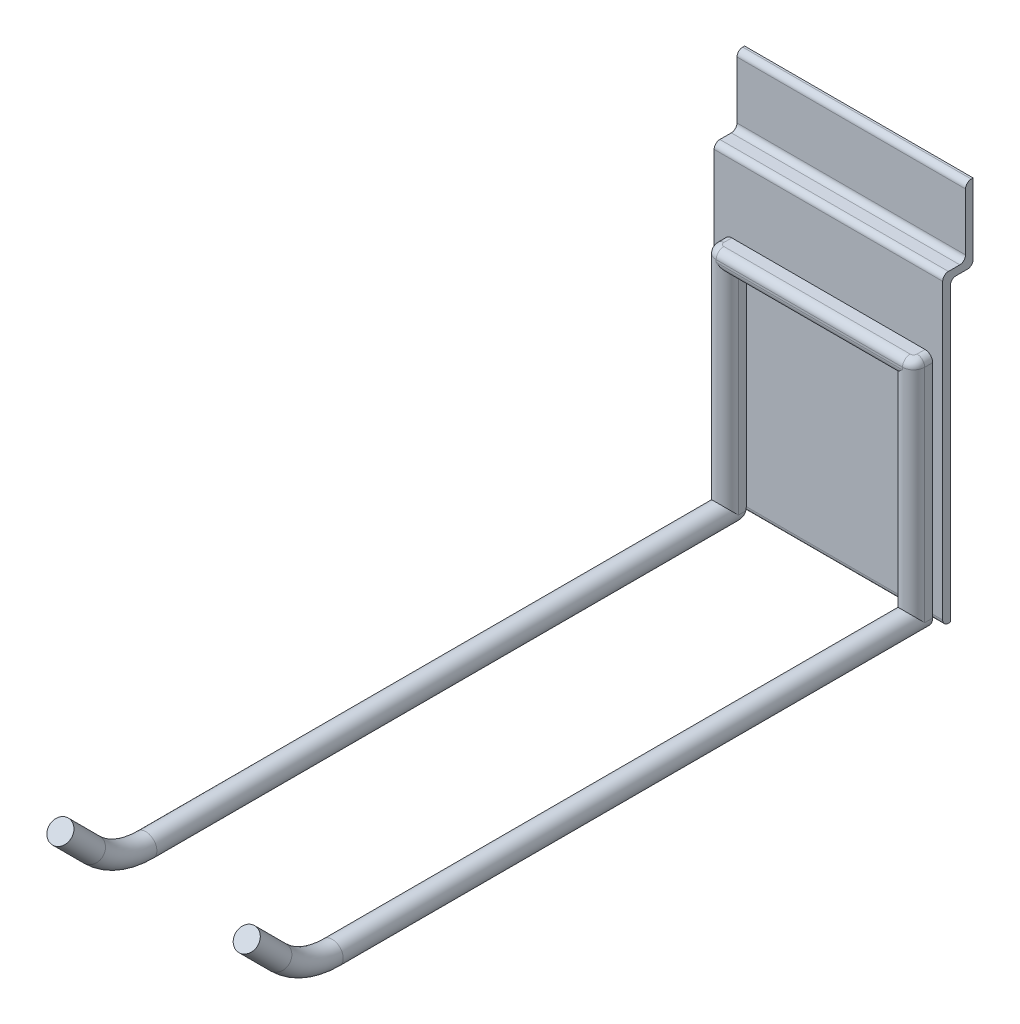
SolidWorks part; units mm, degrees
ref_plane "Front Plane" through (0, 0, 0) normal (0, 0, 1) x (1, 0, 0)
ref_plane "Top Plane" through (0, 0, 0) normal (0, 1, 0) x (1, 0, 0)
ref_plane "Right Plane" through (0, 0, 0) normal (1, 0, 0) x (0, 0, -1)
sketch "Sketch1" plane through (0, 0, 0) normal (0, 0, 1) x (1, 0, 0)
  line L1 (0, 0) -> (76.2, 0)
  line L2 (0, 0) -> (0, -101.6)
  line L3 (0, -101.6) -> (76.2, -101.6)
  line L4 (76.2, 0) -> (76.2, -101.6)
  dimension "D1" = 101.6
  dimension "D2" = 76.2
extrude "Boss-Extrude1" add sketch "Sketch1" along normal blind 2.54
sketch "Sketch3" plane through (0, 0, 0) normal (0, 0, -1) x (-1, 0, 0)
  line L0 (0, 0) -> (0, -101.6) construction
  line L1 (-76.2, 0) -> (0, 0)
  line L2 (-76.2, 0) -> (-76.2, -2.54)
  line L3 (-76.2, -2.54) -> (0, -2.54)
  line L4 (0, 0) -> (0, -2.54)
  dimension "D1" = 2.54
extrude "Boss-Extrude3" add sketch "Sketch3" along normal blind 7.62
sketch "Sketch4" plane through (0, 0, 0) normal (0, 1, 0) x (1, 0, 0)
  line L0 (76.2, -2.54) -> (76.2, 7.62) construction
  line L1 (0, 7.62) -> (76.2, 7.62)
  line L2 (0, 7.62) -> (0, 5.08)
  line L3 (0, 5.08) -> (76.2, 5.08)
  line L4 (76.2, 7.62) -> (76.2, 5.08)
  dimension "D1" = 2.54
extrude "Boss-Extrude4" add sketch "Sketch4" along normal blind 22.86
fillet "Fillet3" radius 1.905 6 edges at (38.1, -101.6, 2.54) (38.1, 0, 2.54) (38.1, 0, -5.08) (38.1, 22.86, -5.08) (38.1, -2.54, -7.62) (38.1, -2.54, 0)
sketch "Sketch5" plane through (0, 0, 2.54) normal (0, 0, 1) x (1, 0, 0)
  line L0 (3.3436, -104.5061) -> (3.3436, -24.5234)
  line L1 (3.3436, -24.5234) -> (72.8564, -24.5234)
  line L2 (72.8564, -24.5234) -> (72.8564, -104.5061)
  line L3 (72.8564, -104.5061) -> (65.476, -104.5061)
  line L4 (65.476, -104.5061) -> (65.476, -30.3591)
  line L5 (65.476, -30.3591) -> (10.724, -30.3591)
  line L6 (10.724, -30.3591) -> (10.724, -104.5061)
  line L7 (10.724, -104.5061) -> (3.3436, -104.5061)
  line L8 (38.1, -30.3591) -> (38.1, -99.695) construction
  line L9 (0, -99.695) -> (76.2, -99.695) construction
extrude "Boss-Extrude5" add sketch "Sketch5" along normal blind 6.35
sketch "Sketch6" plane through (0, 0, 8.89) normal (0, 0, 1) x (1, 0, 0)
  line L0 (3.3436, -104.5061) -> (10.724, -104.5061) construction
  circle A0 centre (7.0338, -100.8159) radius 3.6902
sketch3d "3DSketch1"
  line L0 (7.0338, -100.8159, 8.89) -> (7.0338, -100.8159, 199.0574)
  line L1 (7.0338, -93.3764, 217.0179) -> (7.0338, -82.8554, 227.5389)
  arc A0 (7.0338, -100.8159, 199.0574) -> (7.0338, -93.3764, 217.0179) centre (7.0338, -75.4159, 199.0574) ccw
  point P6 (7.0338, -100.8159, 209.5784)
  point P7 (-18.3662, -75.4159, 199.0574)
  dimension "D1" = 25.4
  dimension "D2" = 25.4
sweep "Sweep1" add profiles "Sketch6" path "3DSketch1"
ref_plane "Plane1" through (38.1, 0, 0) normal (-1, 0, 0) x (0, 0, 1)
mirror "Mirror1" about plane through (38.1, 0, 0) normal (-1, 0, 0) of "Sweep1"
fillet "Fillet4" radius 3.6902 3 edges at (72.8564, -62.6697, 8.89) (69.1662, -97.1257, 8.89) (65.476, -65.5875, 8.89)
fillet "Fillet5" radius 3.6902 3 edges at (10.724, -65.5875, 8.89) (7.0338, -97.1257, 8.89) (3.3436, -62.6697, 8.89)
fillet "Fillet7" radius 2.54 6 edges at (72.8564, -24.5234, 3.8699) (71.7756, -24.5234, 7.8092) (3.3436, -24.5234, 3.8699) (4.4244, -24.5234, 7.8092) (38.1, -24.5234, 8.89) (38.1, -30.3591, 8.89)
fillet "Fillet8" radius 5.08 1 edges at (7.0338, -104.5061, 2.54)
sketch "Sketch7" plane through (0, 0, 8.89) normal (0, 0, 1) x (1, 0, 0)
  line L0 (3.3436, -100.8159) -> (3.3436, -104.5847)
  line L3 (10.724, -104.5847) -> (10.724, -100.8159)
  line L8 (3.3436, -104.5847) -> (10.724, -104.5847)
  line L9 (65.476, -100.8159) -> (65.476, -104.7101)
  line L10 (65.476, -104.7101) -> (72.8564, -104.7101)
  line L11 (72.8564, -104.7101) -> (72.8564, -100.8159)
  arc A4 (3.3436, -100.8159) -> (10.724, -100.8159) centre (7.0338, -100.8159) ccw
  arc A5 (72.8564, -100.8159) -> (65.476, -100.8159) centre (69.1662, -100.8159) cw
extrude "Cut-Extrude1" cut sketch "Sketch7" against normal up to surface (8.89 mm away) up to face at (38.1, -53.0225, 0)
